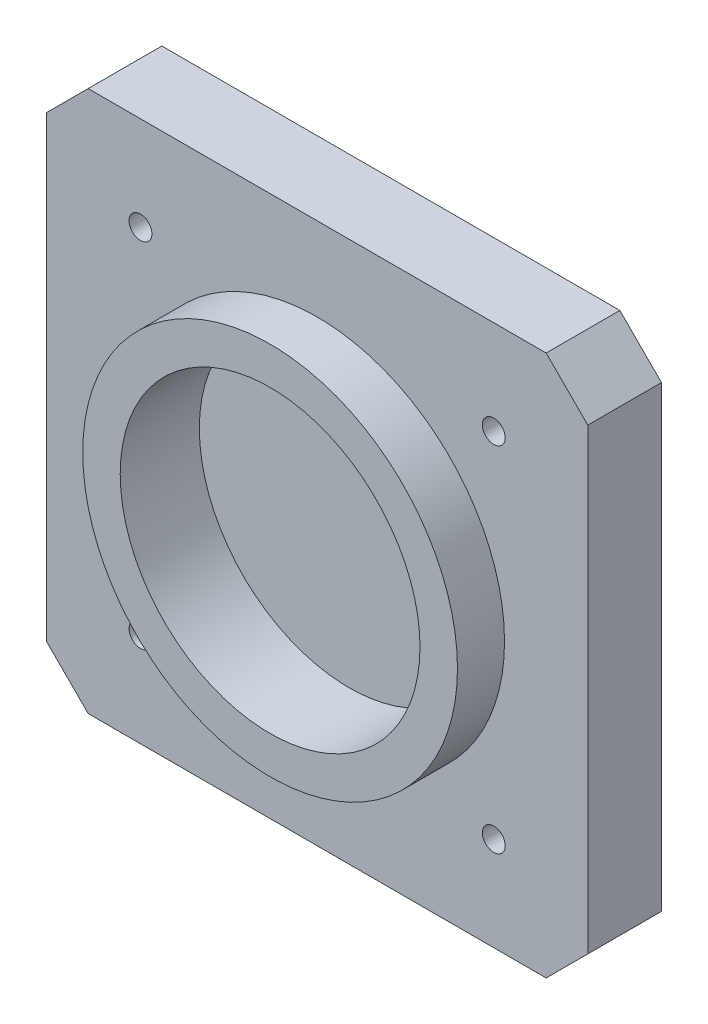
SolidWorks part; units mm, degrees
material "A6061"
ref_plane "前视基准面" through (0, 0, 0) normal (0, 0, 1) x (1, 0, 0)
ref_plane "上视基准面" through (0, 0, 0) normal (0, 1, 0) x (1, 0, 0)
ref_plane "右视基准面" through (0, 0, 0) normal (1, 0, 0) x (0, 0, -1)
sketch "草图1" plane through (0, 0, 0) normal (0, 0, 1) x (1, 0, 0)
  line L1 (65, 65) -> (-65, 65)
  line L2 (65, 65) -> (65, -65)
  line L3 (65, -65) -> (-65, -65)
  line L4 (-65, 65) -> (-65, -65)
  line L5 (65, 65) -> (-65, -65) construction
  line L6 (65, -65) -> (-65, 65) construction
  circle A0 centre (0, 0) radius 36
  circle A1 centre (0, 0) radius 45
  circle A2 centre (0, 0) radius 60 construction
  circle A3 centre (-42.4264, 42.4264) radius 2.5
  circle A4 centre (42.4264, 42.4264) radius 2.5
  circle A5 centre (42.4264, -42.4264) radius 2.5
  circle A6 centre (-42.4264, -42.4264) radius 2.5
  point P20 (0, 0)
  dimension "D1" = 72
  dimension "D2" = 90
  dimension "D3" = 5
  dimension "D4" = 120
  dimension "D6" = 130
  dimension "D5" = 4
extrude "凸台-拉伸1" add sketch "草图1" along normal blind 19 contours A1 A0 region at (-43.7272, 0, 0)
extrude "凸台-拉伸2" add sketch "草图1<3>" against normal blind 10 contours L1 L4 L3 L2 A6 A5 A4 A3 A1 | A1 A0 | A0 region at (63.1615, 0, 0) region at (0, 0, 0) region at (-43.7272, 0, 0)
sketch "草图1<3>" plane through (0, 0, 0) normal (0, 0, 1) x (1, 0, 0) same geometry as "草图1"
extrude "凸台-拉伸3" add sketch "草图1<4>" along normal blind 7.7 contours L1 L4 L3 L2 A6 A5 A4 A3 A1 region at (63.1615, 0, 0)
sketch "草图1<4>" plane through (0, 0, 0) normal (0, 0, 1) x (1, 0, 0) same geometry as "草图1"
hole_wizard "打孔尺寸(%根据)内六角圆柱头螺钉的类型1" positions "草图2" profile "草图3" counterbore size "M5" standard "GB" end condition through all
sketch "草图2" plane through (0, 0, -10) normal (0, 0, -1) x (-1, 0, 0)
  point P0 (42.4264, 42.4264)
  point P3 (-42.4264, 42.4264)
  point P6 (42.4264, -42.4264)
  point P9 (-42.4264, -42.4264)
sketch "草图3" plane through (-42.4264, 42.4264, -10) normal (1, 0, 0) x (0, 1, 0)
  line L0 (0, 0) -> (0, 29)
  line L1 (0, 29) -> (2.75, 29)
  line L3 (2.75, 29) -> (2.75, 5.7)
  line L4 (2.75, 5.7) -> (5, 5.7)
  line L5 (5, 5.7) -> (5, 0)
  line L7 (5, 0) -> (0, 0)
  line L11 (0, -6.35) -> (0, 107.95) construction
  dimension "通孔孔直径" = 5.5
  dimension "通孔孔深度" = 29
  dimension "柱形沉头孔直径" = 10
  dimension "柱形沉头孔深度" = 5.7
chamfer "倒角1" distance 10 angle 45 4 edges at (-65, -65, -1.15) (-65, 65, -1.15) (65, -65, -1.15) (65, 65, -1.15)
